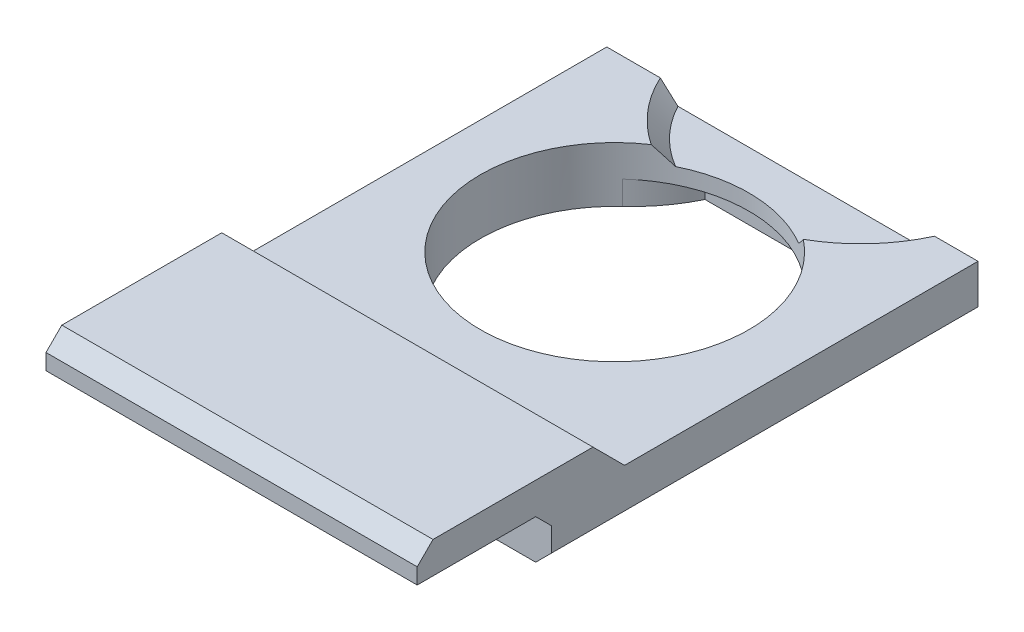
SolidWorks part; units mm, degrees
ref_plane "Front Plane" through (0, 0, 0) normal (0, 0, 1) x (1, 0, 0)
ref_plane "Top Plane" through (0, 0, 0) normal (0, 1, 0) x (1, 0, 0)
ref_plane "Right Plane" through (0, 0, 0) normal (1, 0, 0) x (0, 0, -1)
sketch "Sketch1" plane through (0, 0, 0) normal (0, 1, 0) x (1, 0, 0)
  line L1 (-13.2044, 11.1596) -> (10.2956, 11.1596)
  line L2 (-13.2044, 11.1596) -> (-13.2044, -16.8404)
  line L3 (-13.2044, -16.8404) -> (10.2956, -16.8404)
  line L4 (10.2956, 11.1596) -> (10.2956, -16.8404)
  dimension "D1" = 23.5
  dimension "D2" = 28
extrude "Boss-Extrude1" add sketch "Sketch1" along normal blind 3.5
chamfer "Chamfer1" distance 1 angle 45 3 edges at (-13.2044, 0, 2.8404) (10.2956, 0, 2.8404) (-1.4544, 0, -11.1596)
sketch "Sketch2" plane through (0, 3.5, 0) normal (0, 1, 0) x (1, 0, 0)
  line L0 (10.2956, -16.8404) -> (10.2956, 11.1596) construction
  line L1 (-13.2044, -16.8404) -> (10.2956, -16.8404) construction
  circle A0 centre (-1.7044, -0.8404) radius 8.5
  dimension "D1" = 17
  dimension "D2" = 12
  dimension "D3" = 16
extrude "Cut-Extrude1" cut sketch "Sketch2" against normal blind 3.5
sketch "Sketch3" plane through (0, 3.5, 0) normal (0, 1, 0) x (1, 0, 0)
  circle A0 centre (-1.1353, 14.1562) radius 9.5555
extrude "Cut-Extrude3" cut sketch "Sketch3" against normal blind 1
chamfer "Chamfer2" distance 1 angle 45 2 edges at (6.246, 2.5, -8.0879) (-8.7414, 2.5, -8.3721)
sketch "Sketch4" plane through (0, 3.5, 0) normal (0, 1, 0) x (1, 0, 0)
  line L0 (-13.2044, 11.1596) -> (-13.2044, -16.8404) construction
  line L1 (-13.2044, -14.2139) -> (10.2956, -14.2139)
  line L2 (-13.2044, -14.2139) -> (-13.2044, -23.3404)
  line L3 (-13.2044, -23.3404) -> (10.2956, -23.3404)
  line L4 (10.2956, -14.2139) -> (10.2956, -23.3404)
  line L5 (10.2956, -16.8404) -> (10.2956, 11.1596) construction
  line L6 (-13.2044, -16.8404) -> (10.2956, -16.8404) construction
  dimension "D1" = 0
  dimension "D2" = 6.5
extrude "Boss-Extrude2" add sketch "Sketch4" along normal blind 2
chamfer "Chamfer3" distance 2 angle 45 1 edges at (-1.4544, 3.5, 14.2139)
chamfer "Chamfer4" distance 1 angle 45 1 edges at (-1.4544, 3.5, 16.8404)
sketch "Sketch5" plane through (0, 0, 0) normal (0, -1, 0) x (1, 0, 0)
  line L1 (-5.2318, -5.5128) -> (2.2706, -5.5128)
  line L2 (-5.2318, -5.5128) -> (-5.2318, -8.4048)
  line L3 (-5.2318, -8.4048) -> (2.2706, -8.4048)
  line L4 (2.2706, -5.5128) -> (2.2706, -8.4048)
extrude "Cut-Extrude4" cut sketch "Sketch5" against normal blind 1.5
fillet "Fillet1" radius 10 2 edges at (2.2706, 0.75, -6.6729) (-5.2318, 0.75, -6.8931)
sketch "Sketch6" plane through (0, 0, 23.3404) normal (0, 0, 1) x (1, 0, 0)
  line L4 (-13.2044, 3.5) -> (10.2956, 3.5)
  line L5 (10.2956, 3.5) -> (10.2956, 5.5)
  line L6 (10.2956, 5.5) -> (-13.2044, 5.5)
  line L7 (-13.2044, 5.5) -> (-13.2044, 3.5)
  line L8 (-13.2044, 3.5) -> (10.2956, 3.5)
  line L9 (10.2956, 3.5) -> (10.2956, 5.5)
  line L10 (10.2956, 5.5) -> (-13.2044, 5.5)
  line L11 (-13.2044, 5.5) -> (-13.2044, 3.5)
  dimension "D1" = 0
extrude "Boss-Extrude3" add sketch "Sketch6" along normal blind 2
sketch "Sketch7" plane through (0, 3.5, 0) normal (0, 1, 0) x (1, 0, 0)
  line L0 (10.2956, 11.1596) -> (7.9382, 11.1596) construction
  line L1 (-14.6352, 12.0638) -> (11.101, 12.0638)
  line L2 (-14.6352, 12.0638) -> (-14.6352, 10.1596)
  line L3 (-14.6352, 10.1596) -> (11.101, 10.1596)
  line L4 (11.101, 12.0638) -> (11.101, 10.1596)
  dimension "D1" = 1
extrude "Cut-Extrude6" cut sketch "Sketch7" against normal blind 7
chamfer "Chamfer5" distance 1 angle 45 1 edges at (-1.4544, 5.5, 25.3404)
